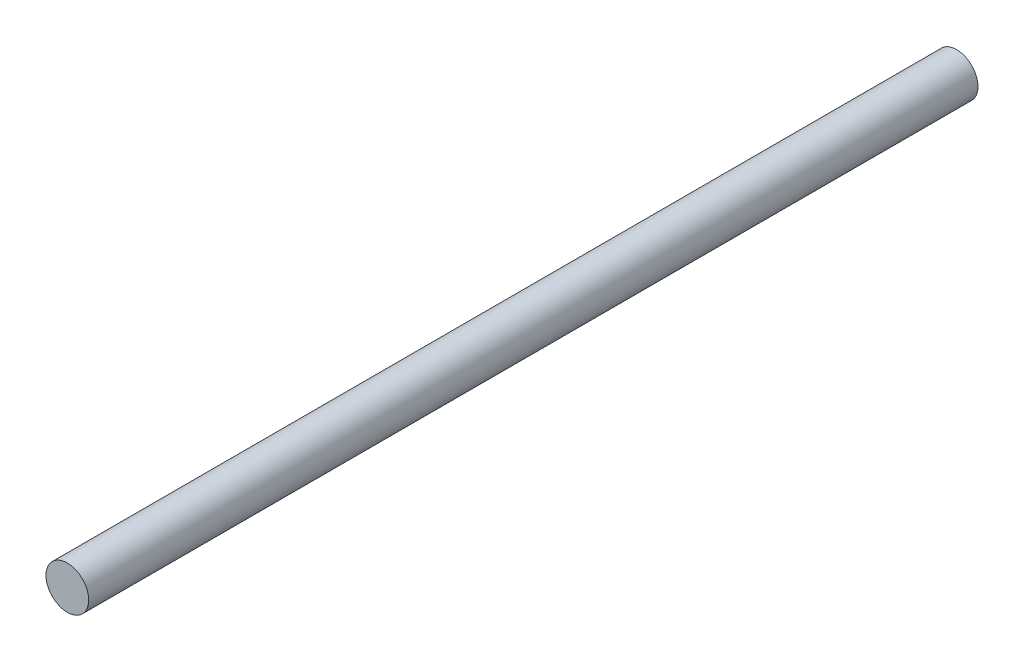
SolidWorks part; units mm, degrees
ref_plane "Front Plane" through (0, 0, 0) normal (0, 0, 1) x (1, 0, 0)
ref_plane "Top Plane" through (0, 0, 0) normal (0, 1, 0) x (1, 0, 0)
ref_plane "Right Plane" through (0, 0, 0) normal (1, 0, 0) x (0, 0, -1)
sketch "Sketch1" plane through (0, 0, 0) normal (0, 0, 1) x (1, 0, 0)
  circle A0 centre (0, 0) radius 3.9687
  dimension "D1" = 7.9375
extrude "Boss-Extrude1" add sketch "Sketch1" along normal blind 165.1
